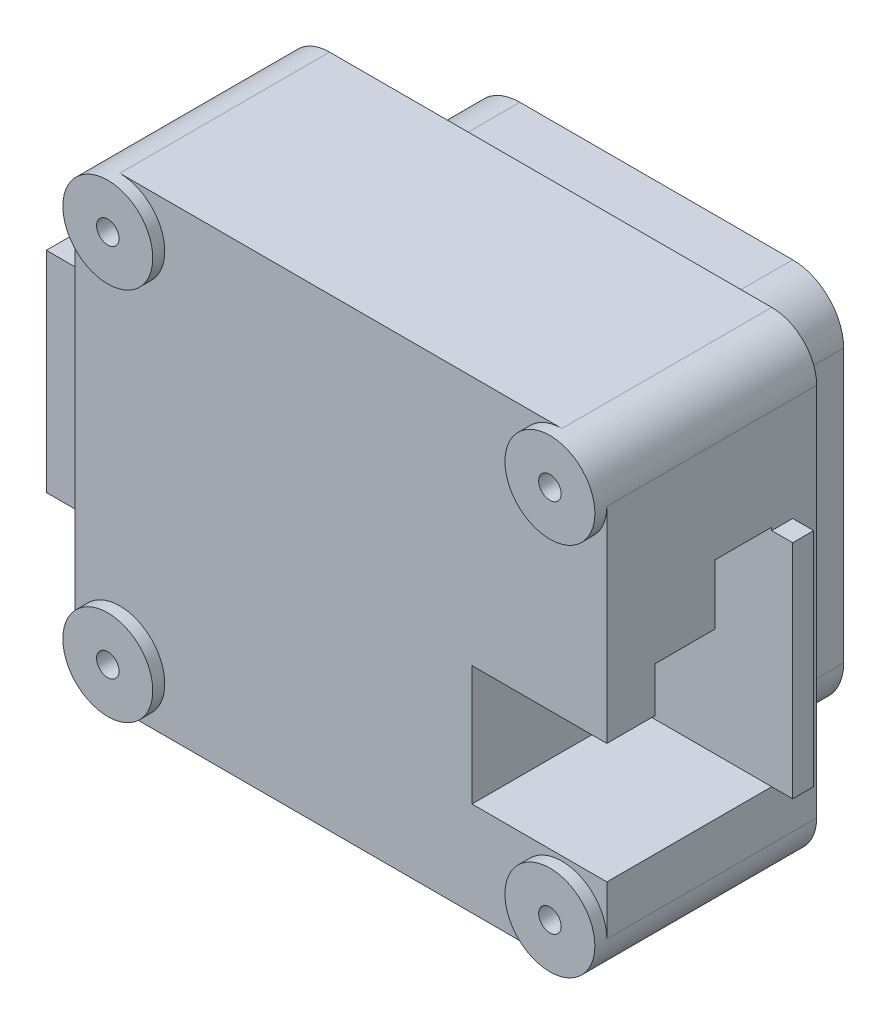
SolidWorks part; units mm, degrees
ref_plane "Front Plane" through (0, 0, 0) normal (0, 0, 1) x (1, 0, 0)
ref_plane "Top Plane" through (0, 0, 0) normal (0, 1, 0) x (1, 0, 0)
ref_plane "Right Plane" through (0, 0, 0) normal (1, 0, 0) x (0, 0, -1)
sketch "Sketch1" plane through (0, 0, 0) normal (0, 0, 1) x (1, 0, 0)
  line L10 (0, 0) -> (35.5, 0)
  line L14 (0, 31) -> (35.5, 31)
  line L17 (35.5, 0) -> (35.5, 6.3)
  line L18 (35.5, 21.3) -> (26.5, 21.3)
  line L20 (35.5, 6.3) -> (26.5, 6.3)
  line L21 (26.5, 21.3) -> (26.5, 6.3)
  line L22 (35.5, 31) -> (35.5, 21.3)
  line L24 (0, 31) -> (0, 0)
  point P8 (0, 31)
  point P14 (35.5, 31)
  point P17 (0, 31)
  point P19 (35.5, 0)
  point P20 (35.5, 31)
  dimension "D9" = 9
  dimension "D2" = 35.5
  dimension "D3" = 31
  dimension "D10" = 6.3
  dimension "D11" = 15
extrude "Boss-Extrude1" add sketch "Sketch1" along normal blind 14
sketch "Sketch10" plane through (0, 0, 0) normal (-1, 0, 0) x (0, 0, 1)
  line L0 (0, 31) -> (0, 0) construction
  line L1 (0, 22.5) -> (12.4, 22.5)
  line L2 (0, 22.5) -> (0, 8.5)
  line L3 (0, 8.5) -> (12.4, 8.5)
  line L4 (12.4, 22.5) -> (12.4, 8.5)
  line L5 (14, 31) -> (0, 31) construction
  dimension "D1" = 12.4
  dimension "D2" = 14
  dimension "D3" = 8.5
extrude "Boss-Extrude5" add sketch "Sketch10" along normal blind 3.5
sketch "Sketch11" plane through (-3.5, 0, 0) normal (-1, 0, 0) x (0, 0, 1)
  line L0 (12.4, 22.5) -> (0, 8.5) construction
  line L1 (0, 22.5) -> (12.4, 8.5) construction
  circle A0 centre (6.2, 15.5) radius 3
  dimension "D1" = 6
extrude "Boss-Extrude6" add sketch "Sketch11" against normal blind 1.5
extrude "Cut-Extrude1" cut sketch "Sketch11<2>" against normal blind 1.6
sketch "Sketch11<2>" plane through (-3.5, 0, 0) normal (-1, 0, 0) x (0, 0, 1) same geometry as "Sketch11"
sketch "Sketch12" plane through (26.5, 0, 0) normal (1, 0, 0) x (0, 0, -1)
  line L0 (-14, 6.3) -> (0, 6.3) construction
  line L1 (0, 21.3) -> (-3, 21.3)
  line L2 (0, 21.3) -> (0, 6.3)
  line L3 (0, 6.3) -> (-3, 6.3)
  line L4 (-3, 21.3) -> (-3, 6.3)
  dimension "D1" = 3
extrude "Boss-Extrude7" add sketch "Sketch12" along normal blind 9
sketch "Sketch13" plane through (26.5, 0, 0) normal (1, 0, 0) x (0, 0, -1)
  line L1 (-14, 21.3) -> (-10.8, 21.3)
  line L2 (-14, 21.3) -> (-14, 14.3)
  line L3 (-14, 14.3) -> (-10.8, 14.3)
  line L4 (-10.8, 21.3) -> (-10.8, 14.3)
  dimension "D1" = 7
  dimension "D2" = 3.2
extrude "Boss-Extrude8" add sketch "Sketch13" along normal blind 9
fillet "Fillet1" radius 3 4 edges at (0, 0, 7) (35.5, 0, 7) (35.5, 31, 7) (0, 31, 7)
sketch "Sketch15" plane through (0, 0, 14) normal (0, 0, 1) x (1, 0, 0)
  line L2 (17.75, 0) -> (17.75, 23.0381) construction
  line L3 (3, 0) -> (32.5, 0) construction
  line L4 (0, 15.5) -> (26.6234, 15.5) construction
  line L5 (0, 28) -> (0, 3) construction
  circle A0 centre (32.5, 3) radius 3
  circle A1 centre (3, 3) radius 3
  circle A2 centre (3, 28) radius 3
  circle A3 centre (32.5, 28) radius 3
  arc A5 (3, 31) -> (0, 28) centre (3, 28) ccw construction
  arc A6 (0, 3) -> (3, 0) centre (3, 3) ccw construction
  arc A7 (35.5, 28) -> (32.5, 31) centre (32.5, 28) ccw construction
  arc A8 (32.5, 0) -> (35.5, 3) centre (32.5, 3) ccw construction
extrude "Boss-Extrude10" add sketch "Sketch15" along normal blind 0.8
sketch "Sketch16" plane through (0, 0, 14.8) normal (0, 0, 1) x (1, 0, 0)
  circle A0 centre (3, 28) radius 0.75
  circle A1 centre (3, 3) radius 0.75
  circle A2 centre (32.5, 3) radius 0.75
  circle A3 centre (32.5, 28) radius 0.75
  circle A4 centre (32.5, 28) radius 3 construction
  dimension "D1" = 1.5
  dimension "D2" = 1.5
  dimension "D3" = 1.5
  dimension "D4" = 1.5
extrude "Cut-Extrude2" cut sketch "Sketch16" against normal blind 5
sketch "Sketch17" plane through (26.5, 0, 0) normal (1, 0, 0) x (0, 0, -1)
  line L0 (-10.8, 21.3) -> (-3, 21.3) construction
  line L1 (-6.8, 21.3) -> (-10.8, 21.3)
  line L2 (-6.8, 21.3) -> (-6.8, 17.3)
  line L3 (-6.8, 17.3) -> (-10.8, 17.3)
  line L4 (-10.8, 21.3) -> (-10.8, 17.3)
  line L5 (-10.8, 14.3) -> (-10.8, 21.3) construction
  dimension "D1" = 4
  dimension "D2" = 4
extrude "Boss-Extrude11" add sketch "Sketch17" along normal blind 9
sketch "Sketch18" plane through (0, 0, 0) normal (0, 0, -1) x (-1, 0, 0)
  line L0 (-35.5, 3) -> (-35.5, 28) construction
  line L1 (-9.3863, 3.15) -> (-27.6, 3.15)
  line L2 (-6, 6.5363) -> (-6, 24.75)
  line L3 (-9.4, 28.15) -> (-27.6, 28.15)
  line L4 (-31, 6.55) -> (-31, 24.75)
  line L5 (-3, 0) -> (-32.5, 0) construction
  arc A0 (-9.3863, 3.15) -> (-6, 6.5363) centre (-9.3863, 6.5363) ccw
  arc A1 (-27.6, 3.15) -> (-31, 6.55) centre (-27.6, 6.55) cw
  arc A2 (-6, 24.75) -> (-9.4, 28.15) centre (-9.4, 24.75) ccw
  arc A3 (-27.6, 28.15) -> (-31, 24.75) centre (-27.6, 24.75) ccw
  point P10 (-6, 3.15)
  point P14 (-31, 3.15)
  point P19 (-31, 28.15)
  dimension "D5" = 3.3863
  dimension "D6" = 3.4
  dimension "D7" = 3.4
  dimension "D1" = 25
  dimension "D2" = 25
  dimension "D3" = 4.5
  dimension "D4" = 3.15
extrude "Boss-Extrude12" add sketch "Sketch18" along normal blind 6.3
sketch "Sketch19" plane through (0, 0, -6.3) normal (0, 0, -1) x (-1, 0, 0)
  line L0 (-6, 15.6431) -> (-31, 15.65) construction
  line L1 (-6, 6.5363) -> (-6, 24.75) construction
  line L2 (-31, 24.75) -> (-31, 6.55) construction
  circle A0 centre (-18.5, 15.6466) radius 11.8
  point P8 (-18.5, 15.6466)
  dimension "D1" = 23.6
extrude "Cut-Extrude3" cut sketch "Sketch19" against normal blind 4
sketch "Sketch20" plane through (0, 0, -2.3) normal (0, 0, -1) x (-1, 0, 0)
  line L0 (-18.4931, 3.15) -> (-18.5, 28.15) construction
  line L1 (-9.4, 28.15) -> (-27.6, 28.15) construction
  line L3 (-27.6, 3.15) -> (-9.3863, 3.15) construction
  circle A2 centre (-18.4966, 15.65) radius 8
  point P9 (-18.5, 28.15)
  point P15 (-18.4931, 3.15)
  dimension "D1" = 16
extrude "Boss-Extrude13" add sketch "Sketch20" along normal blind 4
sketch "Sketch23" plane through (35.5, 0, 0) normal (1, 0, 0) x (0, 0, -1)
  line L1 (-1.6, 21.1) -> (-3, 21.1)
  line L2 (-1.6, 21.1) -> (-1.6, 6.3)
  line L3 (-1.6, 6.3) -> (-3, 6.3)
  line L4 (-3, 21.1) -> (-3, 6.3)
  line L8 (-14, 6.3) -> (-3, 6.3) construction
  line L9 (-3, 21.3) -> (-3, 6.3) construction
  dimension "D1" = 14.8
  dimension "D2" = 1.4
extrude "Boss-Extrude14" add sketch "Sketch23" along normal blind 1.4
sketch "Sketch24" plane through (-3.5, 0, 0) normal (-1, 0, 0) x (0, 0, 1)
  point P0 (6.2, 15.5)
